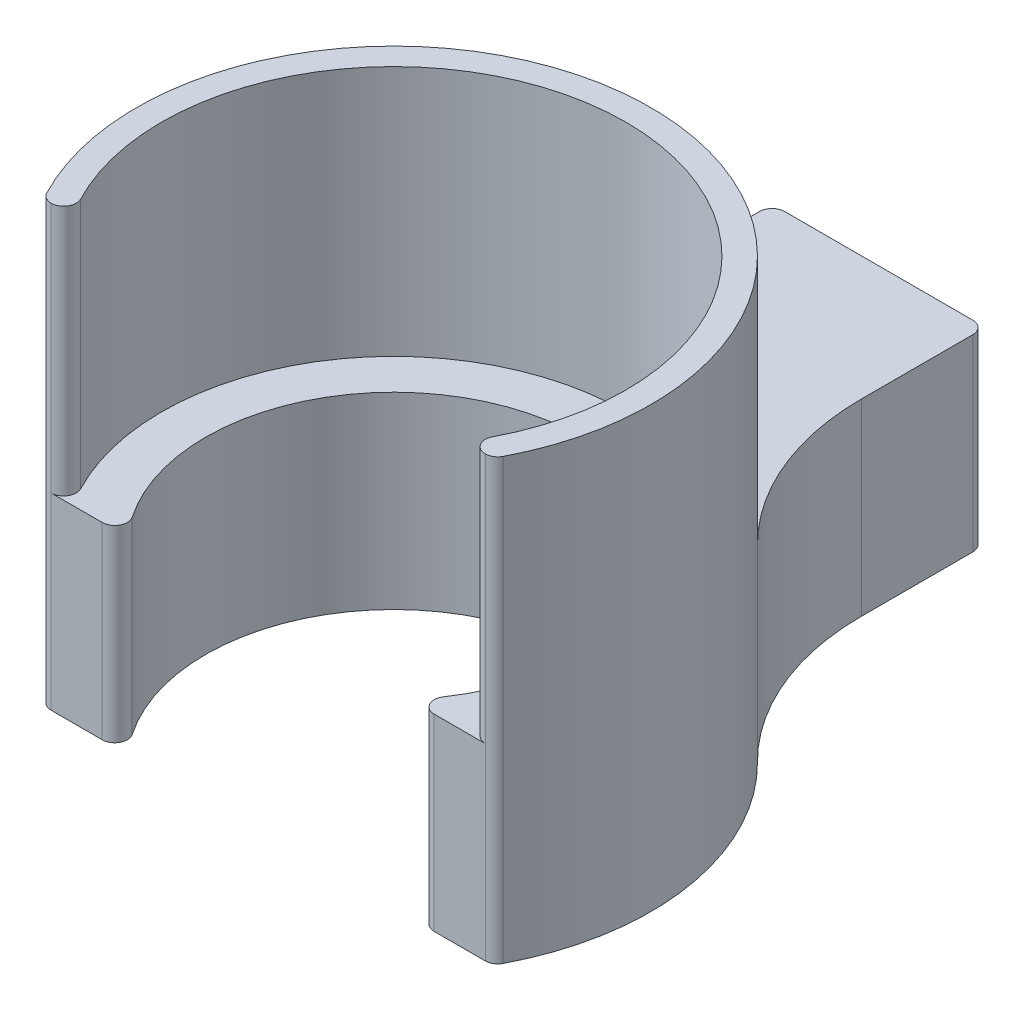
SolidWorks part; units mm, degrees
ref_plane "Plan de face" through (0, 0, 0) normal (0, 0, 1) x (1, 0, 0)
ref_plane "Plan de dessus" through (0, 0, 0) normal (0, 1, 0) x (1, 0, 0)
ref_plane "Plan de droite" through (0, 0, 0) normal (1, 0, 0) x (0, 0, -1)
sketch "Esquisse1" plane through (0, 0, 0) normal (0, 0, 1) x (1, 0, 0)
  line L1 (-8.5, -7.5) -> (8.5, -7.5)
  line L2 (-8.5, -7.5) -> (-8.5, 7.5)
  line L3 (-8.5, 7.5) -> (8.5, 7.5)
  line L4 (8.5, -7.5) -> (8.5, 7.5)
  line L5 (-8.5, -7.5) -> (8.5, 7.5) construction
  line L6 (-8.5, 7.5) -> (8.5, -7.5) construction
  point P0 (0, 0)
  dimension "D1" = 17
  dimension "D2" = 15
extrude "Boss.-Extru.1" add sketch "Esquisse1" along normal blind 20
hole_wizard "Trous de centrage Ø5.0mm1" positions "Esquisse2" profile "Esquisse3" hole size "Ø5.0" standard "AS"
sketch "Esquisse2" plane through (0, 0, 0) normal (0, 0, -1) x (-1, 0, 0)
  line L0 (0, 6.6) -> (0, -6.6) construction
  line L1 (11, 0) -> (-11, 0) construction
  point P0 (0, 0)
sketch "Esquisse3" plane through (0, 0, 0) normal (1, 0, 0) x (0, 1, 0)
  line L0 (0, 0) -> (0, 11.5022)
  line L1 (0, 11.5022) -> (2.5, 10)
  line L2 (2.5, 10) -> (2.5, 0)
  line L5 (2.5, 0) -> (0, 0)
  line L10 (0, 11.5022) -> (-2.5, 10) construction
  line L11 (0, -6.35) -> (0, 107.95) construction
  dimension "Diamètre du perçage" = 5
  dimension "Profondeur du perçage" = 10
  dimension "Angle de pointe" = 118
sketch "Esquisse4" plane through (0, 7.5, 0) normal (0, 1, 0) x (1, 0, 0)
  line L0 (-17.8955, -48.6548) -> (-15.5644, -48.6548)
  line L1 (15.5644, -48.6548) -> (17.8955, -48.6548)
  arc A0 (17.8955, -48.6548) -> (-17.8955, -48.6548) centre (0, -38.6548) ccw
  arc A1 (15.5644, -48.6548) -> (-15.5644, -48.6548) centre (0, -38.6548) ccw
  dimension "D1" = 37
  dimension "D2" = 2
  dimension "D3" = 10
extrude "Boss.-Extru.2" add sketch "Esquisse4" along normal blind 20
sketch "Esquisse5" plane through (0, 7.5, 0) normal (0, -1, 0) x (1, 0, 0)
  line L0 (-15.5644, 48.6548) -> (-11.1803, 48.6548)
  line L1 (-8.5, 20) -> (8.5, 20)
  line L2 (-8.5, 20) -> (8.5, 20)
  line L3 (15.5644, 48.6548) -> (11.1803, 48.6548)
  line L5 (17.8955, 48.6548) -> (15.5644, 48.6548)
  line L6 (17.8955, 48.6548) -> (15.5644, 48.6548)
  line L7 (-15.5644, 48.6548) -> (-17.8955, 48.6548)
  line L8 (-15.5644, 48.6548) -> (-17.8955, 48.6548)
  arc A0 (-11.1803, 48.6548) -> (11.1803, 48.6548) centre (0, 38.6548) ccw
  arc A1 (8.5, 20) -> (17.8955, 48.6548) centre (0, 38.6548) ccw
  arc A2 (8.5, 20) -> (17.8955, 48.6548) centre (0, 38.6548) ccw
  arc A6 (-15.5644, 48.6548) -> (15.5644, 48.6548) centre (0, 38.6548) ccw
  arc A8 (-17.8955, 48.6548) -> (-8.5, 20) centre (0, 38.6548) ccw
  arc A9 (-17.8955, 48.6548) -> (-8.5, 20) centre (0, 38.6548) ccw
  dimension "D2" = 30
  dimension "D1" = 0
extrude "Boss.-Extru.3" add sketch "Esquisse5" along normal up to surface (15 mm away) up to face at (0, -7.5, 10)
fillet "Congé1" radius 20 2 edges at (-8.5, 0, 20) (8.5, 0, 20)
fillet "Congé2" radius 1 8 edges at (17.8955, 10, 48.6548) (15.5644, 17.5, 48.6548) (11.1803, 0, 48.6548) (-11.1803, 0, 48.6548) (-15.5644, 17.5, 48.6548) (-17.8955, 10, 48.6548) (-8.5, 0, 0) (8.5, 0, 0)
